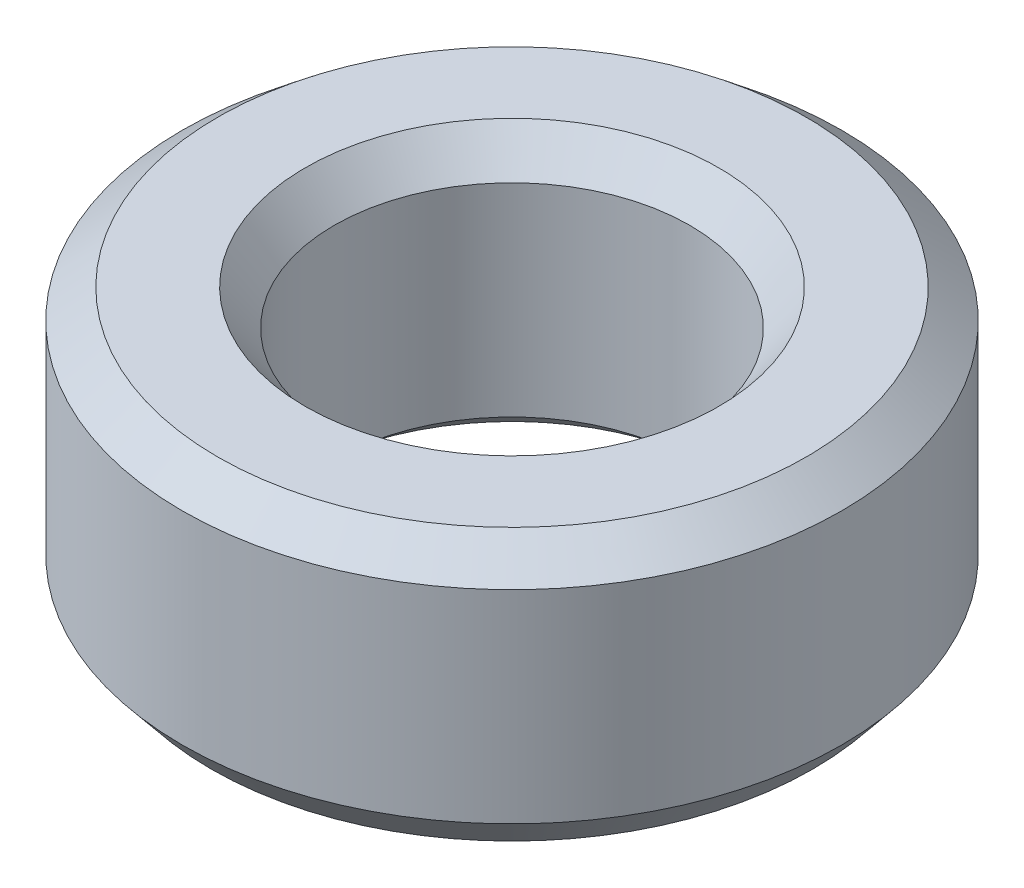
SolidWorks part; units mm, degrees
ref_plane "Front Plane" through (0, 0, 0) normal (0, 0, 1) x (1, 0, 0)
ref_plane "Top Plane" through (0, 0, 0) normal (0, 1, 0) x (1, 0, 0)
ref_plane "Right Plane" through (0, 0, 0) normal (1, 0, 0) x (0, 0, -1)
sketch "Sketch1" plane through (0, 0, 0) normal (0, 1, 0) x (1, 0, 0)
  circle A0 centre (0, 0) radius 27.5
  dimension "SLEEVE_OD" = 55
extrude "Boss-Extrude1" add sketch "Sketch1" along normal blind 22.2829
sketch "Sketch2" plane through (0, 0, 0) normal (0, 1, 0) x (1, 0, 0)
  circle A0 centre (0, 0) radius 14.8302
  dimension "BORE_D" = 29.6605
extrude "Cut-Extrude1" cut sketch "Sketch2" along normal through all
chamfer "Chamfer1" distance 2.4149 angle 50.718 4 edges at (0, 22.2829, 14.8302) (0, 0, 14.8302) (0, 0, 27.5) (0, 22.2829, 27.5) first distance on face at (0, 22.2829, 14.8302) first distance on face at (0, 0, 14.8302) first distance on face at (0, 22.2829, 27.5)
